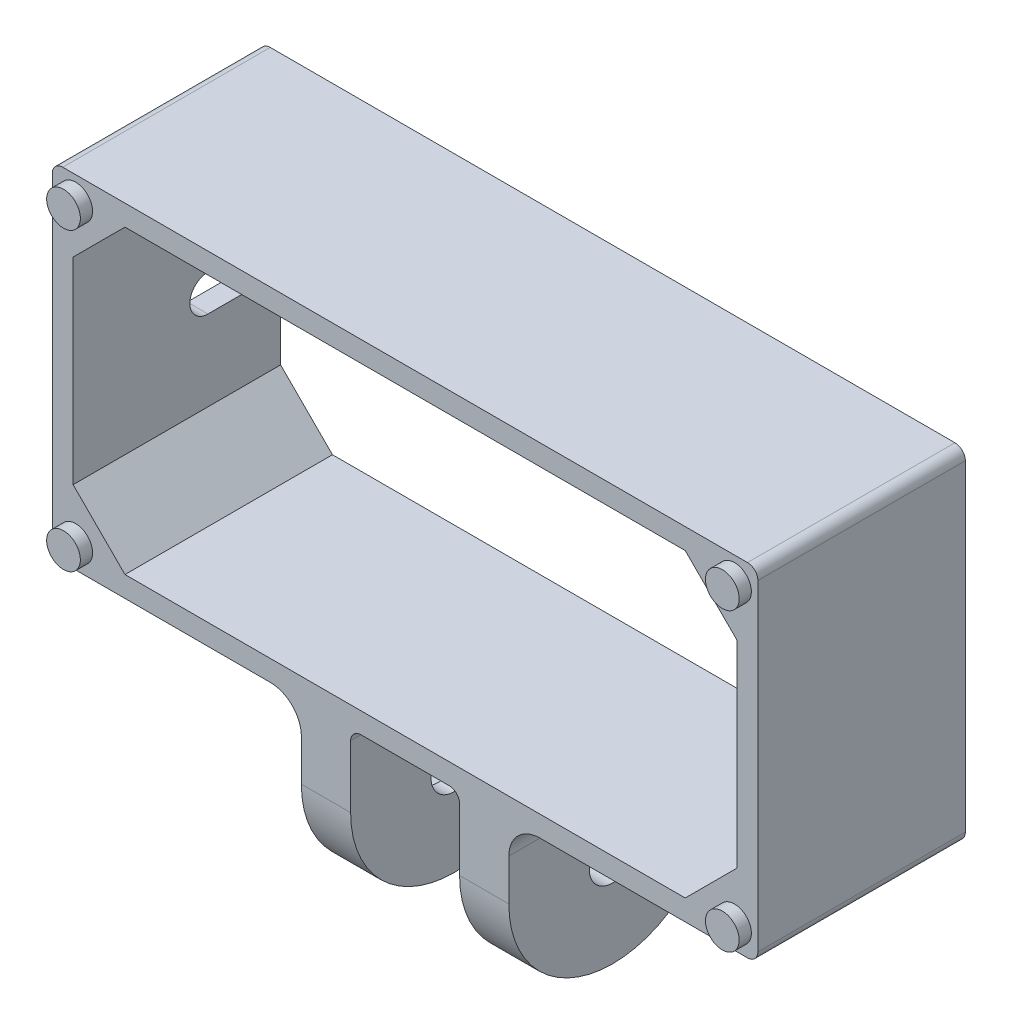
SolidWorks part; units mm, degrees
ref_plane "Front Plane" through (0, 0, 0) normal (0, 0, 1) x (1, 0, 0)
ref_plane "Top Plane" through (0, 0, 0) normal (0, 1, 0) x (1, 0, 0)
ref_plane "Right Plane" through (0, 0, 0) normal (1, 0, 0) x (0, 0, -1)
sketch "Sketch1" plane through (0, 0, 0) normal (0, 0, 1) x (1, 0, 0)
  line L0 (-27, 14.5) -> (-32, 9.5)
  line L1 (27, 14.5) -> (-27, 14.5)
  line L2 (32, 9.5) -> (32, -9.5)
  line L3 (27, -14.5) -> (-27, -14.5)
  line L4 (-32, 9.5) -> (-32, -9.5)
  line L5 (32, 14.5) -> (-32, -14.5) construction
  line L6 (32, -14.5) -> (-32, 14.5) construction
  line L7 (27, 14.5) -> (32, 9.5)
  line L8 (32, -9.5) -> (27, -14.5)
  line L9 (-27, -14.5) -> (-32, -9.5)
  line L11 (-34, 16.5) -> (34, 16.5)
  line L12 (-34, 16.5) -> (-34, -16.5)
  line L13 (-34, -16.5) -> (34, -16.5)
  line L14 (34, 16.5) -> (34, -16.5)
  line L15 (-34, 16.5) -> (34, -16.5) construction
  line L16 (-34, -16.5) -> (34, 16.5) construction
  point P0 (0, 0)
  point P14 (0, 0)
  dimension "D1" = 29
  dimension "D2" = 64
  dimension "D3" = 2
  dimension "D4" = 2
extrude "Boss-Extrude1" add sketch "Sketch1" along normal blind 20
sketch "Sketch2" plane through (0, 0, 20) normal (0, 0, 1) x (1, 0, 0)
  line L0 (29.5, -12) -> (34, -16.5) construction
  line L1 (27, -14.5) -> (32, -9.5) construction
  line L2 (55, 0) -> (-55, 0) construction
  line L3 (0, -55) -> (0, 55) construction
  circle A0 centre (31.75, -14.25) radius 1.625
  circle A1 centre (31.75, 14.25) radius 1.625
  circle A2 centre (-31.75, 14.25) radius 1.625
  circle A3 centre (-31.75, -14.25) radius 1.625
  dimension "D1" = 3.25
extrude "Boss-Extrude2" add sketch "Sketch2" along normal blind 1.175
fillet "Fillet1" radius 1 4 edges at (34, -16.5, 10) (34, 16.5, 10) (-34, -16.5, 10) (-34, 16.5, 10)
sketch "Sketch3" plane through (-34, 0, 0) normal (-1, 0, 0) x (0, 0, 1)
  line L0 (7, 15.5) -> (7, -15.5) construction
  line L1 (20, 15.5) -> (0, 15.5) construction
  line L2 (0, -15.5) -> (20, -15.5) construction
  line L3 (0, 15.5) -> (0, -15.5) construction
  line L4 (7, 0) -> (-7, 0) construction
  line L5 (7, -1.75) -> (-7, -1.75)
  line L6 (7, 1.75) -> (-7, 1.75)
  arc A0 (7, -1.75) -> (7, 1.75) centre (7, 0) ccw
  arc A1 (-7, 1.75) -> (-7, -1.75) centre (-7, 0) ccw
  point P11 (0, 0)
  dimension "D2" = 1.75
  dimension "D1" = 7
extrude "Cut-Extrude1" cut sketch "Sketch3" against normal blind 13
sketch "Sketch5" plane through (0, -16.5, 0) normal (0, -1, 0) x (1, 0, 0)
  line L0 (0, 0) -> (0, 20) construction
  line L1 (-33, 20) -> (33, 20) construction
  line L2 (-33, 0) -> (33, 0) construction
  line L3 (10, 20) -> (-10, 20)
  line L4 (10, 20) -> (10, 0)
  line L5 (10, 0) -> (-10, 0)
  line L6 (-10, 20) -> (-10, 0)
  line L7 (10, 20) -> (-10, 0) construction
  line L8 (10, 0) -> (-10, 20) construction
  line L9 (-5.25, 20) -> (-5.25, 0)
  line L10 (5.25, 20) -> (5.25, 0)
  point P5 (0, 10)
  line M3 (-33, 0) -> (33, 0)
  line M5 (33, 20) -> (-33, 20)
  dimension "D1" = 20
  dimension "D2" = 5.25
extrude "Boss-Extrude3" add sketch "Sketch5" along normal blind 17 contours L10 L4 M5 M3 | L9 L3 L6 M3 region at (7.625, -16.5, 10) region at (-7.625, -16.5, 10)
sketch "Sketch7" plane through (-10, 0, 0) normal (-1, 0, 0) x (0, 0, 1)
  line L0 (20, -24.5) -> (0, -24.5) construction
  line L1 (20, -33.5) -> (20, -16.5) construction
  line L2 (0, -33.5) -> (0, -16.5) construction
  line L3 (20, -33.5) -> (0, -33.5) construction
  circle A0 centre (10, -24.5) radius 2.25
  dimension "D2" = 4.5
  dimension "D1" = 9
extrude "Cut-Extrude2" cut sketch "Sketch7" against normal through all
sketch "Sketch8" plane through (-10, 0, 0) normal (-1, 0, 0) x (0, 0, 1)
  line L0 (20, -33.5) -> (0, -33.5) construction
  line L1 (5.5544, -24.5) -> (7.7772, -28.35)
  line L2 (7.7772, -28.35) -> (12.2228, -28.35)
  line L3 (12.2228, -28.35) -> (14.4456, -24.5)
  line L4 (14.4456, -24.5) -> (12.2228, -20.65)
  line L5 (12.2228, -20.65) -> (7.7772, -20.65)
  line L6 (7.7772, -20.65) -> (5.5544, -24.5)
  circle A0 centre (10, -24.5) radius 3.85 construction
  dimension "D1" = 7.7
extrude "Cut-Extrude3" cut sketch "Sketch8" against normal blind 3.2
fillet "Fillet2" radius 10 4 edges at (7.625, -33.5, 0) (7.625, -33.5, 20) (-7.625, -33.5, 0) (-7.625, -33.5, 20)
fillet "Fillet4" radius 3 2 edges at (-10, -16.5, 10) (10, -16.5, 10)
fillet "Fillet5" radius 1 2 edges at (-5.25, -16.5, 10) (5.25, -16.5, 10)
